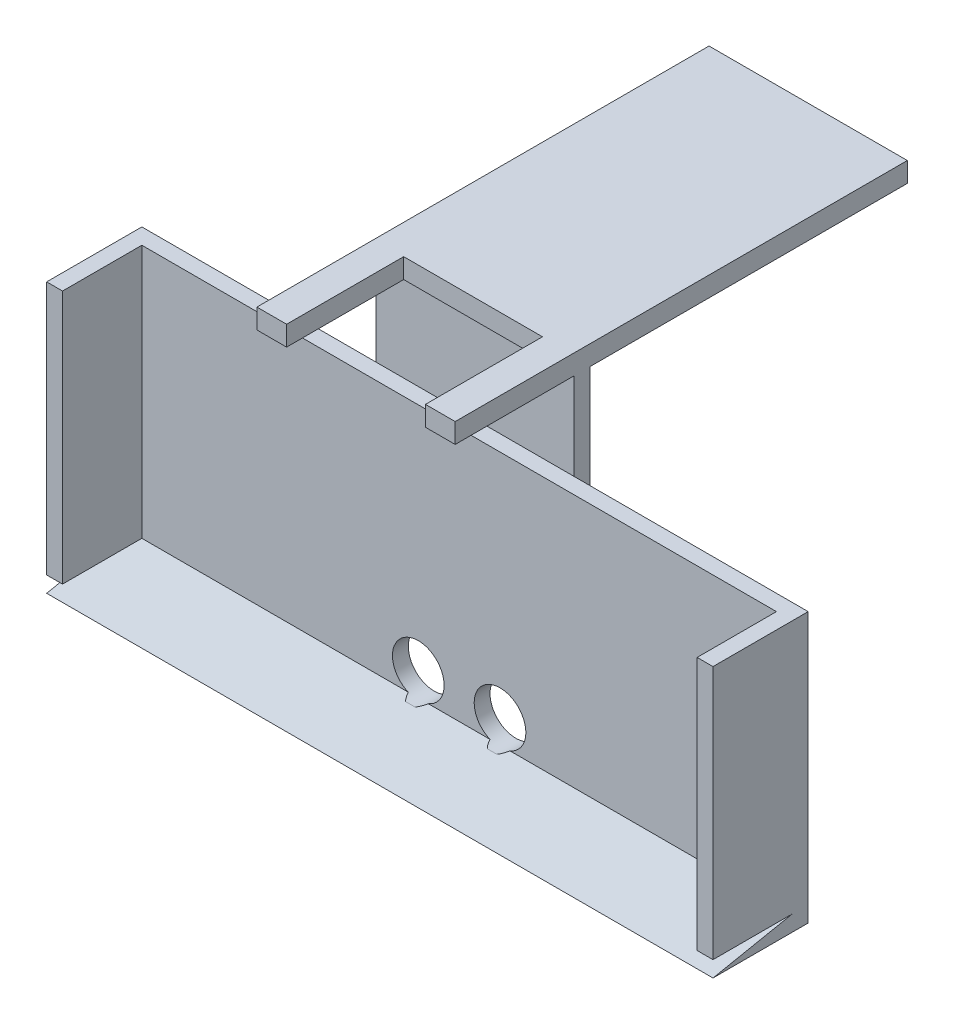
SolidWorks part; units mm, degrees
material "ABS"
ref_plane "Front Plane" through (0, 0, 0) normal (0, 0, 1) x (1, 0, 0)
ref_plane "Top Plane" through (0, 0, 0) normal (0, 1, 0) x (1, 0, 0)
ref_plane "Right Plane" through (0, 0, 0) normal (1, 0, 0) x (0, 0, -1)
sketch "Sketch1" plane through (0, 0, 0) normal (0, 1, 0) x (1, 0, 0)
  line L1 (-101.6, -12.7) -> (101.6, -12.7)
  line L2 (-101.6, -12.7) -> (-101.6, 12.7)
  line L3 (-101.6, 12.7) -> (101.6, 12.7)
  line L4 (101.6, -12.7) -> (101.6, 12.7)
  line L5 (-101.6, -12.7) -> (101.6, 12.7) construction
  line L6 (-101.6, 12.7) -> (101.6, -12.7) construction
  point P0 (0, 0)
  dimension "D1" = 203.2
extrude "Boss-Extrude1" add sketch "Sketch1" along normal blind 5.08 contours L3 L4 L1 L2
ref_plane "Plane1" through (0, 0, 0) normal (1, 0, 0) x (0, 0, -1)
ref_plane "Plane2" through (101.6, 0, 0) normal (1, 0, 0) x (0, 0, -1)
sketch "Sketch4" plane through (101.6, 0, 0) normal (1, 0, 0) x (0, 0, -1)
  line L0 (-12.7, 0) -> (-12.7, 5.08)
  line L1 (-12.7, 5.08) -> (-12.7, 86.36)
  line L2 (-12.7, 86.36) -> (12.7, 86.36)
  line L3 (12.7, 86.36) -> (12.7, 5.08)
  line L4 (12.7, 5.08) -> (12.7, 0)
  line L5 (12.7, 0) -> (-12.7, 0)
extrude "Boss-Extrude2" add sketch "Sketch4" along normal blind 5.08
mirror "Mirror1" about plane through (0, 0, 0) normal (1, 0, 0) of "Boss-Extrude2"
sketch "Sketch5" plane through (0, 0, -12.7) normal (0, 0, -1) x (-1, 0, 0)
  line L1 (-106.68, 86.36) -> (106.68, 86.36)
  line L2 (-106.68, 86.36) -> (-106.68, 0)
  line L3 (-106.68, 0) -> (106.68, 0)
  line L4 (106.68, 86.36) -> (106.68, 0)
extrude "Boss-Extrude3" add sketch "Sketch5" along normal blind 5.08
sketch "Sketch6" plane through (106.68, 0, 0) normal (1, 0, 0) x (0, 0, -1)
  line L0 (-12.7, 0) -> (12.7, 5.08)
  line L4 (12.7, 5.08) -> (-12.7, 5.08)
  line L5 (-12.7, 86.36) -> (-12.7, 0) construction
  line L6 (-12.7, 5.08) -> (-12.7, 0)
  line L7 (-12.7, 0) -> (17.78, 0) construction
  line L8 (17.78, 86.36) -> (17.78, 0) construction
  line L9 (-12.7, 5.08) -> (12.7, 5.08) construction
  dimension "D1" = 5.08
extrude "Cut-Extrude2" cut sketch "Sketch6" against normal through all contours L4 L6 L0
sketch "Sketch7" plane through (0, 0, -17.78) normal (0, 0, -1) x (-1, 0, 0)
  line L0 (-31.75, 50.8) -> (31.75, 50.8)
  line L1 (-106.68, 0) -> (106.68, 0) construction
  line L2 (-31.75, 50.8) -> (-31.75, 114.3)
  line L3 (-31.75, 114.3) -> (31.75, 114.3)
  line L4 (31.75, 114.3) -> (31.75, 50.8)
  point P3 (0, 50.8)
  dimension "D1" = 50.8
  dimension "D2" = 63.5
extrude "Boss-Extrude4" add sketch "Sketch7" along normal blind 5.08 contours L2 L3 L4 L0
sketch "Sketch8" plane through (0, 114.3, 0) normal (0, 1, 0) x (1, 0, 0)
  line L0 (-31.75, 22.86) -> (-31.75, 124.46)
  line L1 (-31.75, 22.86) -> (-31.75, 17.78)
  line L2 (-31.75, 17.78) -> (-31.75, -20.32)
  line L3 (-31.75, -20.32) -> (31.75, -20.32)
  line L4 (31.75, -20.32) -> (31.75, 17.78)
  line L5 (31.75, 17.78) -> (31.75, 22.86)
  line L6 (31.75, 22.86) -> (31.75, 124.46)
  line L7 (31.75, 124.46) -> (-31.75, 124.46)
  dimension "D1" = 101.6
extrude "Boss-Extrude5" add sketch "Sketch8" along normal blind 6.35
sketch "Sketch9" plane through (0, 120.65, 0) normal (0, 1, 0) x (1, 0, 0)
  line L1 (22.225, -41.1636) -> (-22.225, -41.1636)
  line L2 (22.225, -41.1636) -> (22.225, 17.1614)
  line L3 (22.225, 17.1614) -> (-22.225, 17.1614)
  line L4 (-22.225, -41.1636) -> (-22.225, 17.1614)
  point P0 (0, 0)
extrude "Cut-Extrude3" cut sketch "Sketch9" against normal up to next contours L3 L4 L1 L2
sketch "Sketch10" plane through (0, 0, -12.7) normal (0, 0, 1) x (1, 0, 0)
  line L0 (-13.081, 12.7) -> (13.081, 12.7) construction
  line L1 (-106.68, 0) -> (106.68, 0) construction
  circle A0 centre (-13.081, 12.7) radius 8.2697
  circle A1 centre (13.081, 12.7) radius 8.2697
  point P3 (0, 12.7)
  dimension "D1" = 12.7
extrude "Cut-Extrude4" cut sketch "Sketch10" against normal through all and the other way blind 2.54
